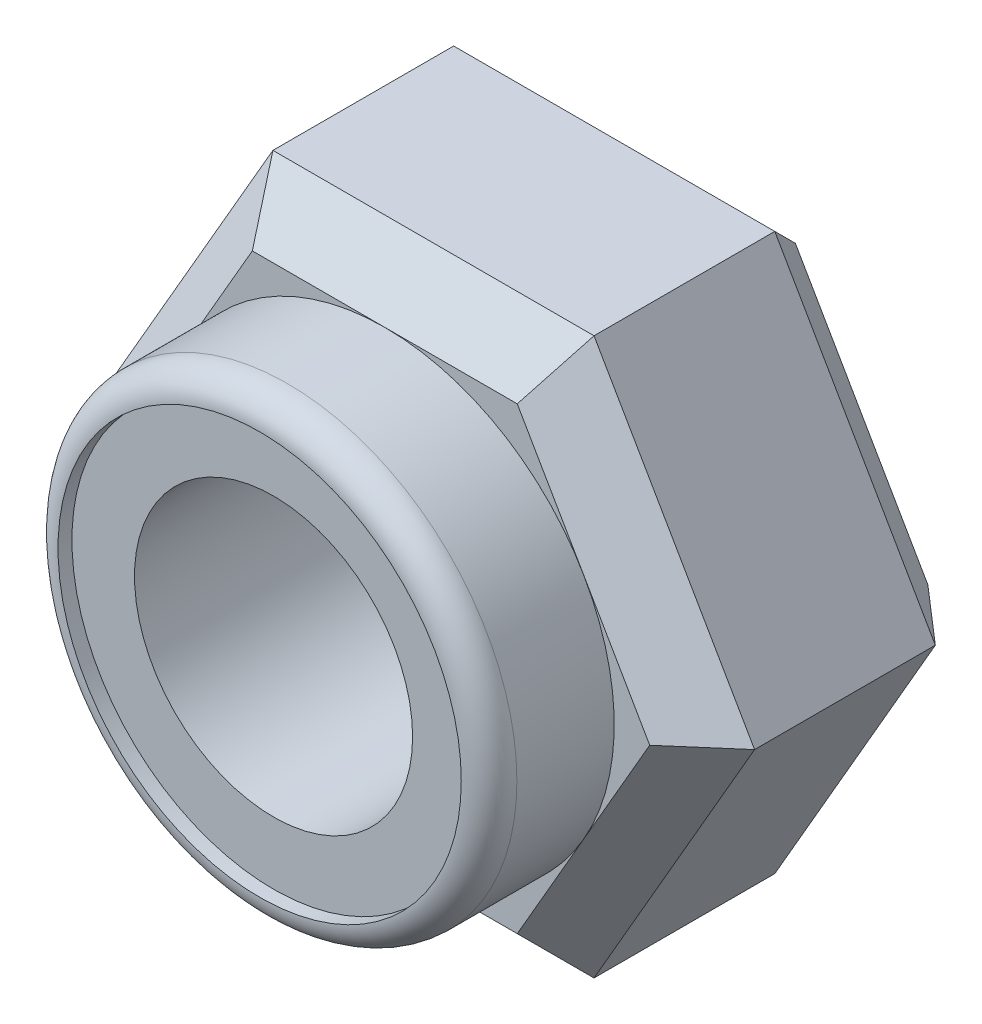
SolidWorks part; units mm, degrees
ref_plane "Front Plane" through (0, 0, 0) normal (0, 0, 1) x (1, 0, 0)
ref_plane "Top Plane" through (0, 0, 0) normal (0, 1, 0) x (1, 0, 0)
ref_plane "Right Plane" through (0, 0, 0) normal (1, 0, 0) x (0, 0, -1)
sketch "Sketch1" plane through (0, 0, 0) normal (0, 0, 1) x (1, 0, 0)
  line L1 (-1.1547, -2) -> (1.1547, -2)
  line L2 (1.1547, -2) -> (2.3094, 0)
  line L3 (2.3094, 0) -> (1.1547, 2)
  line L4 (1.1547, 2) -> (-1.1547, 2)
  line L5 (-1.1547, 2) -> (-2.3094, 0)
  line L6 (-2.3094, 0) -> (-1.1547, -2)
  circle A0 centre (0, 0) radius 2 construction
  circle A1 centre (0, 0) radius 1
  dimension "D2" = 2
  dimension "D1" = 4
extrude "Shape" add sketch "Sketch1" along normal blind 2
chamfer "Chamfer" distance 0.35 angle 45 12 edges at (1.7321, -1, 0) (0, -2, 0) (-1.7321, -1, 0) (-1.7321, 1, 0) (0, 2, 0) (1.7321, 1, 0) (1.7321, 1, 2) (1.7321, -1, 2) (0, -2, 2) (-1.7321, -1, 2) (-1.7321, 1, 2) (0, 2, 2)
ref_axis "Center Axis" through (0, 0, 2) along (0, 0, -1)
sketch "Sketch2" plane through (0, 0, 2) normal (0, 0, 1) x (1, 0, 0)
  line L0 (1.9053, 0) -> (0.9526, 1.65) construction
  circle A0 centre (0, 0) radius 1 construction
  circle A1 centre (0, 0) radius 1
  circle A2 centre (0, 0) radius 1.65
extrude "Boss-Extrude2" add sketch "Sketch2" along normal blind 0.9
fillet "Fillet1" radius 0.2 1 edges at (1.65, 0, 2.9)
sketch "Sketch3" plane through (0, 0, 2.9) normal (0, 0, 1) x (1, 0, 0)
  circle A0 centre (0, 0) radius 1.45 construction
  circle A1 centre (0, 0) radius 1.45
  circle A2 centre (0, 0) radius 1 construction
  circle A3 centre (0, 0) radius 1
extrude "Cut-Extrude1" cut sketch "Sketch3" against normal blind 0.1
